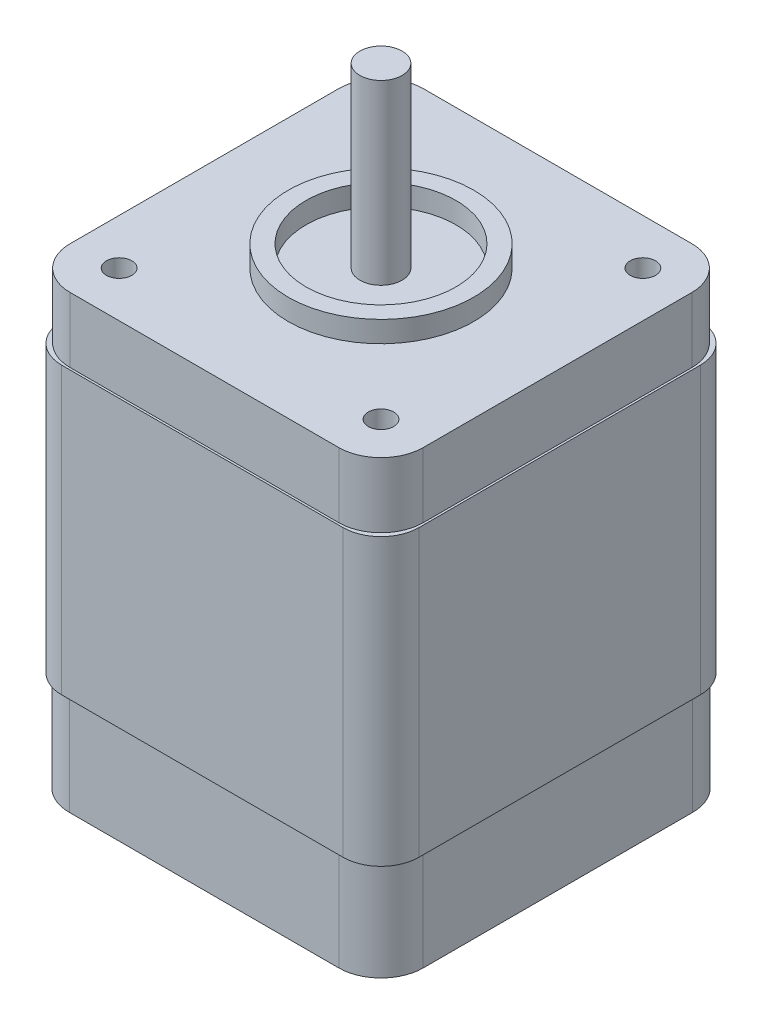
SolidWorks part; units mm, degrees
ref_plane "Front Plane" through (0, 0, 0) normal (0, 0, 1) x (1, 0, 0)
ref_plane "Top Plane" through (0, 0, 0) normal (0, 1, 0) x (1, 0, 0)
ref_plane "Right Plane" through (0, 0, 0) normal (1, 0, 0) x (0, 0, -1)
sketch "Sketch1" plane through (0, 0, 0) normal (0, 1, 0) x (1, 0, 0)
  line L1 (20.95, -20.95) -> (-20.95, -20.95)
  line L2 (20.95, -20.95) -> (20.95, 20.95)
  line L3 (20.95, 20.95) -> (-20.95, 20.95)
  line L4 (-20.95, -20.95) -> (-20.95, 20.95)
  line L5 (20.95, -20.95) -> (-20.95, 20.95) construction
  line L6 (20.95, 20.95) -> (-20.95, -20.95) construction
  point P0 (0, 0)
  dimension "D1" = 41.9
extrude "Boss-Extrude1" add sketch "Sketch1" along normal blind 11.8
sketch "Sketch2" plane through (0, 11.8, 0) normal (0, 1, 0) x (1, 0, 0)
  line L1 (21.15, -21.15) -> (-21.15, -21.15)
  line L2 (21.15, -21.15) -> (21.15, 21.15)
  line L3 (21.15, 21.15) -> (-21.15, 21.15)
  line L4 (-21.15, -21.15) -> (-21.15, 21.15)
  line L5 (21.15, -21.15) -> (-21.15, 21.15) construction
  line L6 (21.15, 21.15) -> (-21.15, -21.15) construction
  point P0 (0, 0)
  dimension "D1" = 42.3
extrude "Boss-Extrude2" add sketch "Sketch2" along normal blind 33.8
sketch "Sketch3" plane through (0, 45.6, 0) normal (0, 1, 0) x (1, 0, 0)
  line L1 (20.9, -20.9) -> (-20.9, -20.9)
  line L2 (20.9, -20.9) -> (20.9, 20.9)
  line L3 (20.9, 20.9) -> (-20.9, 20.9)
  line L4 (-20.9, -20.9) -> (-20.9, 20.9)
  line L5 (20.9, -20.9) -> (-20.9, 20.9) construction
  line L6 (20.9, 20.9) -> (-20.9, -20.9) construction
  point P0 (0, 0)
  dimension "D1" = 41.8
extrude "Boss-Extrude3" add sketch "Sketch3" along normal blind 7.7
sketch "Sketch4" plane through (0, 53.3, 0) normal (0, 1, 0) x (1, 0, 0)
  circle A0 centre (0, 0) radius 10.98
  circle A1 centre (0, 0) radius 8.875
  dimension "D1" = 21.96
  dimension "D2" = 17.75
extrude "Boss-Extrude4" add sketch "Sketch4" along normal blind 2.5
fillet "Fillet1" radius 5 8 edges at (-20.95, 5.9, -20.95) (20.9, 49.45, -20.9) (20.95, 5.9, -20.95) (20.95, 5.9, 20.95) (-20.9, 49.45, 20.9) (-20.95, 5.9, 20.95) (-20.9, 49.45, -20.9) (20.9, 49.45, 20.9)
fillet "Fillet3" radius 4.5 4 edges at (-21.15, 28.7, 21.15) (21.15, 28.7, 21.15) (21.15, 28.7, -21.15) (-21.15, 28.7, -21.15)
sketch "Sketch5" plane through (0, 53.3, 0) normal (0, 1, 0) x (1, 0, 0)
  circle A0 centre (0, 0) radius 2.5
  dimension "D1" = 5
extrude "Boss-Extrude5" add sketch "Sketch5" along normal blind 21
sketch "Sketch6" plane through (0, 53.3, 0) normal (0, 1, 0) x (1, 0, 0)
  line L1 (15.5, 15.5) -> (-15.5, 15.5) construction
  line L2 (15.5, 15.5) -> (15.5, -15.5) construction
  line L3 (15.5, -15.5) -> (-15.5, -15.5) construction
  line L4 (-15.5, 15.5) -> (-15.5, -15.5) construction
  line L5 (15.5, 15.5) -> (-15.5, -15.5) construction
  line L6 (15.5, -15.5) -> (-15.5, 15.5) construction
  circle A0 centre (-15.5, -15.5) radius 1.5
  circle A1 centre (-15.5, 15.5) radius 1.5
  circle A2 centre (15.5, 15.5) radius 1.5
  circle A3 centre (15.5, -15.5) radius 1.5
  point P0 (0, 0)
  dimension "D1" = 3
  dimension "D2" = 31
extrude "Cut-Extrude1" cut sketch "Sketch6" against normal blind 5
sketch "Sketch7" plane through (0, 0, 0) normal (0, -1, 0) x (1, 0, 0)
  line L0 (-20.95, -15.95) -> (-20.95, 15.95) construction
  line L1 (-20.95, 13.5) -> (-23.15, 13.5)
  line L2 (-20.95, 13.5) -> (-20.95, -13.5)
  line L3 (-20.95, -13.5) -> (-23.15, -13.5)
  line L4 (-23.15, 13.5) -> (-23.15, -13.5)
  point P6 (-23.15, 0)
  dimension "D1" = 27
  dimension "D2" = 2.2
extrude "Boss-Extrude6" add sketch "Sketch7" against normal blind 11.8
fillet "Fillet5" radius 3 2 edges at (-20.95, 5.9, 13.5) (-20.95, 5.9, -13.5)
